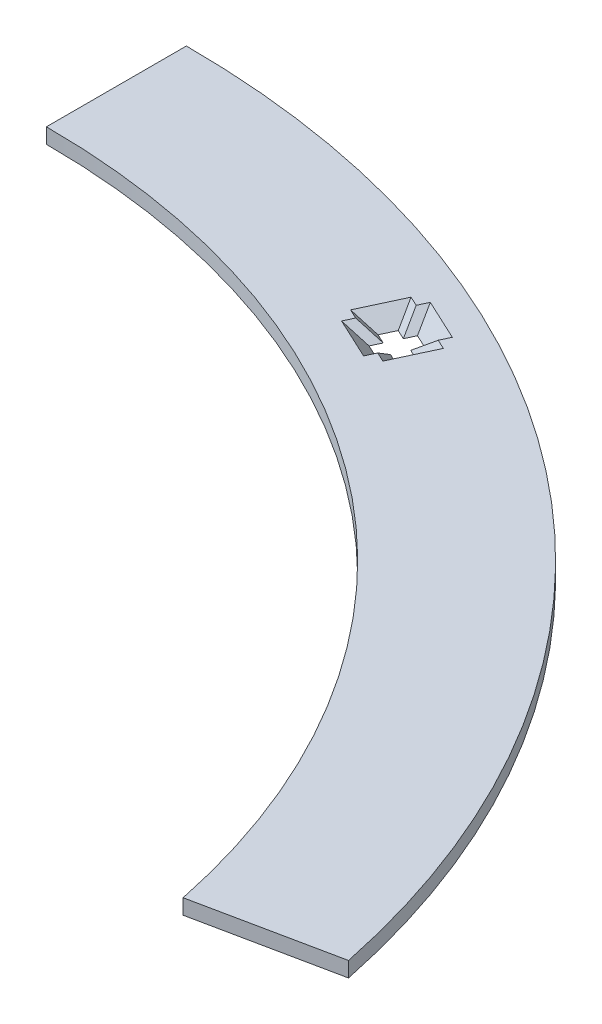
SolidWorks part; units mm, degrees
ref_plane "Front Plane" through (0, 0, 0) normal (0, 0, 1) x (1, 0, 0)
ref_plane "Top Plane" through (0, 0, 0) normal (0, 1, 0) x (1, 0, 0)
ref_plane "Right Plane" through (0, 0, 0) normal (1, 0, 0) x (0, 0, -1)
sketch "Sketch1" plane through (0, 0, 0) normal (0, 1, 0) x (1, 0, 0)
  line L0 (0, 49.519) -> (0, 59.7644)
  line L1 (48.4915, 10.0354) -> (58.5242, 12.1117)
  arc A0 (0, 49.519) -> (48.4915, 10.0354) centre (0, 0) cw
  arc A1 (0, 59.7644) -> (58.5242, 12.1117) centre (0, 0) cw
  dimension "D3" = 10.2453
  dimension "D4" = 59.7644
  dimension "D1" = 67.6789
  dimension "D2" = 81.6814
extrude "Boss-Extrude1" add sketch "Sketch1" along normal blind 1
sketch "Sketch2" plane through (0, 1, 0) normal (0, 1, 0) x (1, 0, 0)
  line L0 (20.9276, 44.8795) -> (25.2575, 54.1649)
  line L1 (19.7397, 45.4334) -> (56.979, 28.0685) construction
  line L2 (0, 59.7644) -> (0, 49.519) construction
  line L3 (23.1466, 50.8211) -> (22.1323, 48.6459)
  line L4 (22.6394, 49.7335) -> (23.5457, 49.3109)
  line L5 (23.0386, 48.2233) -> (24.0529, 50.3985)
  line L6 (24.0529, 50.3985) -> (23.1466, 50.8211)
  line L7 (23.0386, 48.2233) -> (22.1323, 48.6459)
  line L8 (23.0926, 49.5222) -> (47007.7236, 17150.5294) construction
  line L9 (22.2163, 50.4825) -> (21.7937, 49.5762)
  line L10 (23.9688, 48.5619) -> (21.7937, 49.5762)
  line L11 (22.2163, 50.4825) -> (24.3915, 49.4682)
  line L12 (24.3915, 49.4682) -> (23.9688, 48.5619)
  arc A1 (48.4915, 10.0354) -> (0, 49.519) centre (0, 0) ccw construction
  arc A2 (58.5242, 12.1117) -> (0, 59.7644) centre (0, 0) ccw construction
  point P10 (23.0926, 49.5222)
  dimension "D2" = 1.2
  dimension "D1" = 25
  dimension "D3" = 1
  dimension "D4" = 45
extrude "Cut-Extrude1" cut sketch "Sketch2" against normal through all contours L0 L11 L5 L6 | L3 L11 L0 L6 | L11 L3 L4 L0 | L11 L9 L10 L3 | L10 L0 L4 L3 | L0 L10 L3 L7 | L5 L10 L0 L7 | L10 L5 L4 L0 | L12 L11 L5 L10 | L11 L0 L4 L5 region at (22.5068, 1, -48.8575) region at (22.9599, 1, -48.6462) region at (22.7603, 1, -49.4013) region at (23.2135, 1, -49.19) region at (22.9717, 1, -49.8544) region at (23.4248, 1, -49.6431) region at (23.8629, 1, -49.163) region at (22.3222, 1, -49.8814) region at (23.2252, 1, -50.3982) region at (23.6784, 1, -50.1869)
chamfer "Chamfer1" distance 1 angle 45 12 edges at (22.2802, 1, -48.9631) (22.5854, 1, -48.4346) (23.1865, 1, -48.5405) (23.6516, 1, -48.7098) (24.1801, 1, -49.0151) (24.0742, 1, -49.6161) (23.905, 1, -50.0812) (23.5997, 1, -50.6098) (22.9986, 1, -50.5039) (22.5335, 1, -50.3346) (22.005, 1, -50.0293) (22.1109, 1, -49.4283)
sketch "Sketch3" plane through (0, 1, 0) normal (0, 1, 0) x (1, 0, 0)
  circle A0 centre (0, 0) radius 58.7398
  arc A1 (58.5242, 12.1117) -> (0, 59.7644) centre (0, 0) ccw construction
  line M15 (48.4915, 10.0354) -> (58.5242, 12.1117)
  arc M16 (58.5242, 12.1117) -> (0, 59.7644) centre (0, 0) ccw
  line M17 (0, 59.7644) -> (0, 49.519)
  dimension "D1" = 1.0245
extrude "Cut-Extrude2" cut sketch "Sketch3" against normal through all contours A0 M15 M16 M17 region at (37.5659, 1, -46.1363)
equation "\"outer_diameter\"= 26mm"
equation "\"D2@Sketch1\"= \"outer_diameter\" * pi"
equation "\"inner diameter\"= 21.54285714mm"
equation "\"D1@Sketch1\"= \"inner diameter\" * pi"
equation "\"D4@Sketch1\" = \"outer_diameter\" / ( 2 * sin ( 12.5634694 ) )"
equation "\"height\" = 10"
equation "\"D3@Sketch1\" = \"height\" / cos ( 12.5634694 )"
equation "\"D1@Sketch3\"= 1 / cos ( 12.5634694 )"
